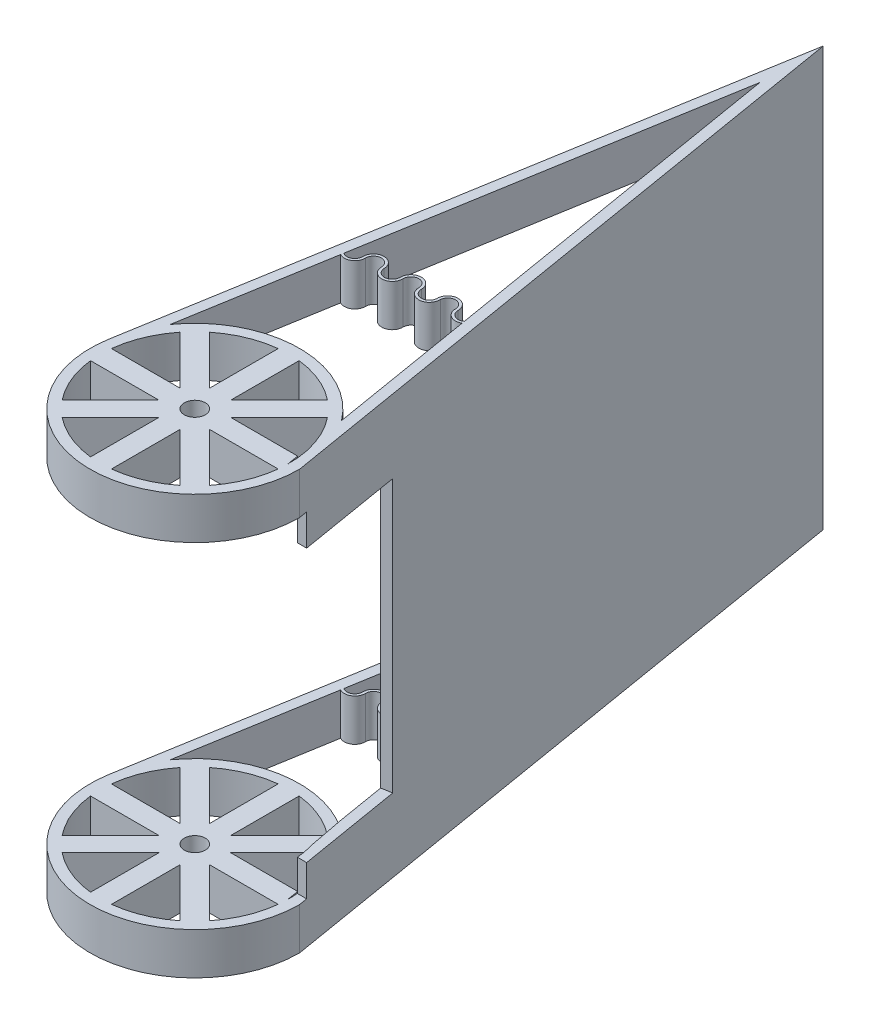
SolidWorks part; units mm, degrees
ref_plane "Front Plane" through (0, 0, 0) normal (0, 0, 1) x (1, 0, 0)
ref_plane "Top Plane" through (0, 0, 0) normal (0, 1, 0) x (1, 0, 0)
ref_plane "Right Plane" through (0, 0, 0) normal (1, 0, 0) x (0, 0, -1)
sketch "Sketch1" plane through (0, 0, 0) normal (0, 1, 0) x (1, 0, 0)
  line L0 (0, 0) -> (0, 60)
  line L1 (0, 60) -> (-9.8601, 1.6667)
  line L2 (0, 60) -> (10, 0)
  line L3 (-0.0069, 53.9589) -> (9.0136, -0.1644)
  line L4 (-0.0069, 53.9589) -> (-8.8741, 1.5)
  line L5 (0, -1) -> (0, -9.0151)
  line L6 (-1, 0) -> (-1, -9.0151)
  line L7 (1, 0) -> (1, -9.0151)
  line L8 (-1, -1) -> (-1, -9.0151) construction
  line L9 (1, -1) -> (1, -9.0151) construction
  line L10 (-0.7071, 0.7071) -> (-7.0817, -5.6675)
  line L11 (0.7071, -0.7071) -> (-5.6675, -7.0817)
  line L12 (0, 1) -> (-9.0151, 1)
  line L13 (0, -1) -> (-9.0151, -1)
  line L14 (0.7071, 0.7071) -> (-5.6675, 7.0817)
  line L15 (-0.7071, -0.7071) -> (-7.0817, 5.6675)
  line L16 (1, 0) -> (1, 9.0151)
  line L17 (-1, 0) -> (-1, 9.0151)
  line L18 (0.7071, -0.7071) -> (7.0817, 5.6675)
  line L19 (-0.7071, 0.7071) -> (5.6675, 7.0817)
  line L20 (0, -1) -> (9.0151, -1)
  line L21 (0, 1) -> (9.0151, 1)
  line L22 (-0.7071, -0.7071) -> (5.6675, -7.0817)
  line L23 (0.7071, 0.7071) -> (7.0817, -5.6675)
  circle A0 centre (0, 0) radius 10
  circle A1 centre (0, 0) radius 9.0151
  circle A2 centre (0, 0) radius 1
  point P49 (0, 0)
  dimension "D2" = 20
  dimension "D4" = 2
  dimension "D1" = 60
  dimension "D3" = 1
  dimension "D5" = 1
  dimension "D6" = 1
  dimension "D7" = 8
extrude "Boss-Extrude1" add sketch "Sketch1" along normal blind 40 contours A0 L4 L3 L0 L1 | A1 L4 A0 L2 L3 | A1 L0 A0 L4 | A1 L3 A0 L0 | A0 L2 L0 L3 | L14 A1 L15 L12 L17 | L12 A1 L13 L10 L15 | L10 A1 L11 L6 L13 | L6 A1 L5 L11 | L5 A1 L7 L22 | L22 A1 L23 L20 L7 | L16 A1 L0 L19 | L0 A1 L17 L14 | L18 A1 L19 L16 L21 | L20 A1 L3 L21 L18 L23 | L6 L15 L10 L13 | L10 L17 L12 L15 | L12 L19 L14 L17 | L14 L21 L16 L19 | L16 L23 L18 L21 | L23 L18 L7 L20 | L11 L22 L7 L20 | L22 L13 L6 L11 | L22 L15 L6 L13 | L6 L17 L10 L15 | L10 L19 L12 L17 | L19 L12 L0 | L0 L21 L14 | L23 L16 L7 L18 | L11 L20 L7 L18 | L20 L5 L11 | L13 L22 L5 | A2 L22 L13 | A2 L20 L11 | A2 L18 L7 | L14 L23 L16 L21 | A2 L14 L21 | A2 L12 L19 | A2 L10 L17 | A2 L6 L15 | A2 L16 L23 region at (-0.1381, 0, -1.1381) region at (-0.3893, 0, -0.9398) region at (0.1381, 0, -1.1381) region at (0.3893, 0, -0.9398) region at (-0.4876, 0, -5.4495) region at (0.6381, 0, -1.5404) region at (-0.6381, 0, -1.5404) region at (0.4876, 0, -5.4495) region at (-0.8047, 0, -0.8047) region at (0.8047, 0, -0.8047) region at (0.9398, 0, -0.3893) region at (-0.9398, 0, -0.3893) region at (-0.5074, 0, -9.1197) region at (4.5299, 0, -7.8401) region at (-3.8534, 0, -3.8534) region at (3.8534, 0, -3.8534) region at (-1.5404, 0, -0.6381) region at (1.5404, 0, -0.6381) region at (1.1381, 0, 0) region at (0.9398, 0, 0.3893) region at (-1.1381, 0, 0) region at (-0.9398, 0, 0.3893) region at (-5.4495, 0, 0) region at (5.4257, 0, 0.004) region at (1.5404, 0, 0.6381) region at (0.8047, 0, 0.8047) region at (0.3893, 0, 0.9398) region at (-1.5404, 0, 0.6381) region at (-0.8047, 0, 0.8047) region at (-0.3893, 0, 0.9398) region at (-4.4504, 0, -30.7592) region at (4.349, 0, -30.9492) region at (8.6047, 0, -4.5717) region at (3.8534, 0, 3.8534) region at (0.6381, 0, 1.5404) region at (0.1381, 0, 1.1381) region at (-0.1381, 0, 1.1381) region at (-3.8534, 0, 3.8534) region at (-0.6381, 0, 1.5404) region at (0.4876, 0, 5.4495) region at (-0.4876, 0, 5.4495)
sketch "Sketch2" plane through (0, 40, 0) normal (0, 1, 0) x (1, 0, 0)
  line L0 (-0.8363, -9.965) -> (17.9794, -14.403)
  arc A0 (-9.8601, 1.6667) -> (10, 0) centre (0, 0) ccw construction
ref_plane "Plane1" through (0, 20, 0) normal (0, -1, 0) x (-1, 0, 0)
sketch "Sketch4" plane through (0, 20, 0) normal (0, -1, 0) x (-1, 0, 0)
  line L1 (0.0069, 53.9589) -> (-7.9823, 6.0236) construction
  line L2 (-8.9782, 0.8144) -> (-12.5014, 0.8144)
  line L7 (0.0069, 53.9589) -> (-7.9823, 6.0236)
  line L8 (-7.9823, 6.0236) -> (-8.9782, 0.8144)
  line L9 (0.0069, 53.9589) -> (27.2562, 53.9589)
  line L10 (27.2562, 53.9589) -> (27.2562, -11.3156)
  line L11 (-12.5014, 0.8144) -> (-12.5014, -9.874)
  line L12 (-12.5014, -9.874) -> (27.2562, -11.3156)
  arc A0 (-8.6454, 2.5551) -> (-8.9782, 0.8144) centre (0, 0) ccw
  arc A5 (-8.7463, 2.0278) -> (-8.8774, 1.3418) centre (0, 0) ccw
extrude "Cut-Extrude2" cut sketch "Sketch4" against normal mid plane 32 contours L8 A5 L10 L9 L7 region at (-10.5643, 20, -19.5562)
sketch "Sketch5" plane through (9.7297, 0, -1.6216) normal (0.9864, 0, -0.1644) x (-0.1644, 0, -0.9864)
  line L0 (-0.8183, 20) -> (9.1817, 20)
  line L1 (-0.8183, 4) -> (-0.8183, 36) construction
  line L2 (-11, 20) -> (11, 20) construction
  line L4 (-0.8183, 33) -> (9.1817, 33)
  line L5 (-0.8183, 33) -> (-0.8183, 7)
  line L6 (-0.8183, 7) -> (9.1817, 7)
  line L7 (9.1817, 33) -> (9.1817, 7)
  line L8 (-0.8183, 33) -> (9.1817, 7) construction
  line L9 (-0.8183, 7) -> (9.1817, 33) construction
  point P6 (4.1817, 20)
  line M5 (-0.8183, 36) -> (-0.8183, 4)
  dimension "D1" = 10
  dimension "D2" = 26
extrude "Cut-Extrude3" cut sketch "Sketch5" against normal mid plane 25.5 contours L7 L0 L6 M5 | L7 L4 L0 M5 region at (9.0423, 26.5, -5.7464) region at (9.0423, 13.5, -5.7464)
sketch "Sketch6" plane through (0, 0, 0) normal (0, -1, 0) x (1, 0, 0)
  line L0 (-5.6476, -20.5881) -> (5.5163, -20.8195)
  line L1 (-0.0069, -53.9589) -> (-8.1476, -5.7979) construction
  line L2 (-0.0069, -53.9589) -> (7.9823, -6.0236) construction
  circle A0 centre (-0.0657, -20.7038) radius 1
  circle A1 centre (-0.0657, -20.7038) radius 0.75
  circle A2 centre (1.6843, -20.7038) radius 0.75
  circle A3 centre (1.6843, -20.7038) radius 1
  circle A4 centre (3.4343, -20.7038) radius 0.75
  circle A5 centre (3.4343, -20.7038) radius 1
  circle A6 centre (5.1843, -20.7038) radius 0.75
  circle A7 centre (5.1843, -20.7038) radius 1
  circle A8 centre (-1.8153, -20.6675) radius 0.75
  circle A9 centre (-1.8153, -20.6675) radius 1
  circle A10 centre (-3.5649, -20.6313) radius 0.75
  circle A11 centre (-3.5649, -20.6313) radius 1
  circle A12 centre (-5.3145, -20.595) radius 0.75
  circle A13 centre (-5.3145, -20.595) radius 1
  line M32 (7.9823, -6.0236) -> (-0.0069, -53.9589)
  line M33 (-0.0069, -53.9589) -> (-8.1476, -5.7979)
  dimension "D3" = 2
  dimension "D4" = 1.5
  dimension "D1" = 15
  dimension "D2" = 15
  dimension "D5" = 4
  dimension "D6" = 4
extrude "Boss-Extrude2" add sketch "Sketch6" against normal blind 4 contours A11 A13 A12 M33 | L0 A13 A11 | A11 A13 L0 | A13 A11 A9 A10 | A9 A11 L0 | L0 A11 A9 | A11 A8 A0 A9 | L0 A9 A0 | A0 A9 L0 | A9 A0 A3 L0 A1 | L0 A3 A0 | A0 A3 L0 | A5 A3 A0 A2 | A3 A5 L0 | L0 A5 A3 | A7 L0 A4 A3 A5 | A5 A7 L0 | L0 A7 A5 | A7 A5 A6 M32 region at (-4.4359, 0, -20.43) region at (-5.0651, 0, -19.8725) region at (-4.4435, 0, -20.7963) region at (-3.5809, 0, -21.4014) region at (-2.6863, 0, -20.4663) region at (-2.6939, 0, -20.8325) region at (-1.795, 0, -19.688) region at (-0.9367, 0, -20.5025) region at (-0.8329, 0, -20.943) region at (-0.9443, 0, -20.8688) region at (1.6843, 0, -19.724) region at (0.8096, 0, -20.5307) region at (0.809, 0, -20.8972) region at (4.3089, 0, -20.9391) region at (3.4343, 0, -21.6839) region at (2.5596, 0, -20.5505) region at (2.5589, 0, -20.9179) region at (4.3096, 0, -20.5697) region at (4.9502, 0, -19.9763)
ref_plane "Plane2" through (0, 20, 0) normal (0, -1, 0) x (-1, 0, 0)
mirror "Mirror2" about plane through (0, 20, 0) normal (0, -1, 0) of "Boss-Extrude2"
